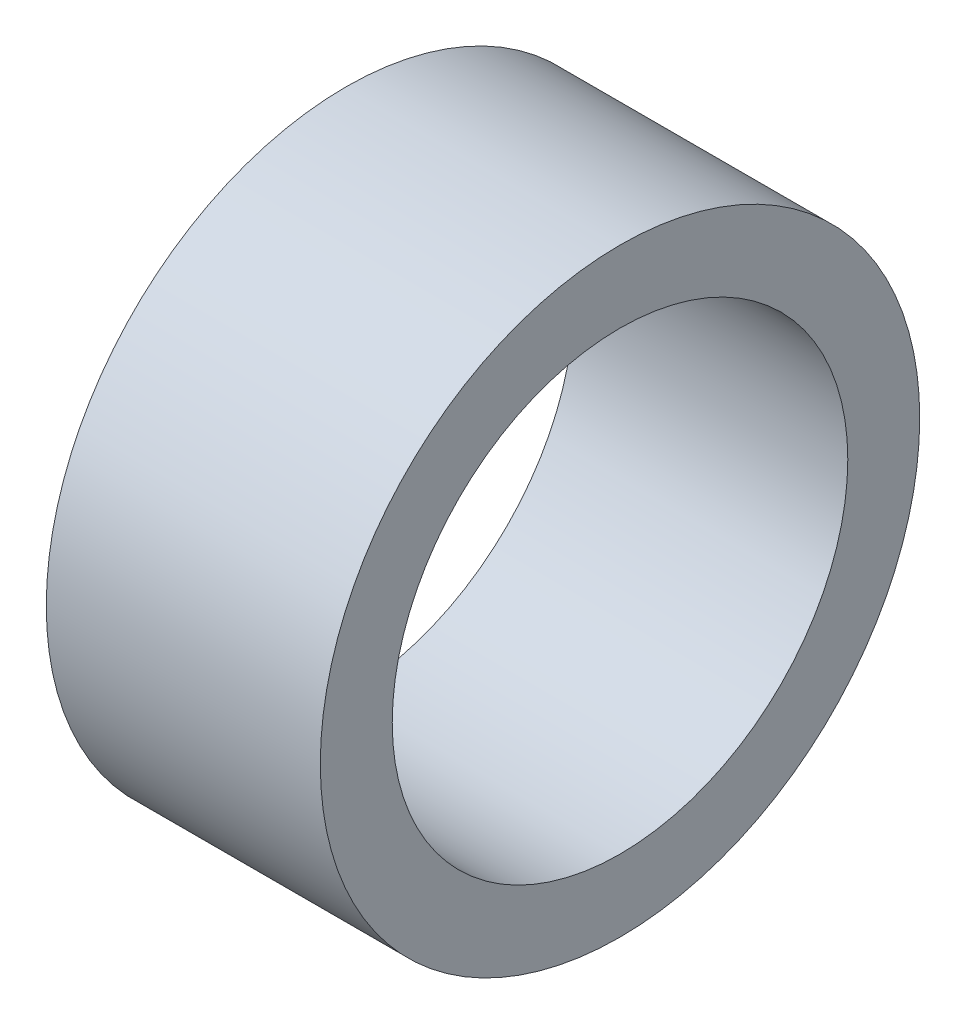
SolidWorks part; units mm, degrees
material "Nylon 6/10"
ref_plane "Front Plane" through (0, 0, 0) normal (0, 0, 1) x (1, 0, 0)
ref_plane "Top Plane" through (0, 0, 0) normal (0, 1, 0) x (1, 0, 0)
ref_plane "Right Plane" through (0, 0, 0) normal (1, 0, 0) x (0, 0, -1)
sketch "Sketch1" plane through (0, 0, 0) normal (0, 0, 1) x (1, 0, 0)
  line L0 (31.75, -13.8602) -> (31.75, 12.314) construction
  line L1 (31.75, 5.5562) -> (36.83, 5.5562)
  line L2 (31.75, 5.5562) -> (31.75, 4.2227)
  line L3 (31.75, 4.2227) -> (36.83, 4.2227)
  line L4 (36.83, 5.5562) -> (36.83, 4.2227)
  line L5 (0, 0) -> (42.6651, 0) construction
  line L7 (50.5354, 3.9688) -> (-48.4378, 3.9688) construction
  dimension "D1" = 0.254
  dimension "D2" = 11.1125
  dimension "D3" = 5.08
revolve "Revolve1" add sketch "Sketch1" angle 360 about L5
